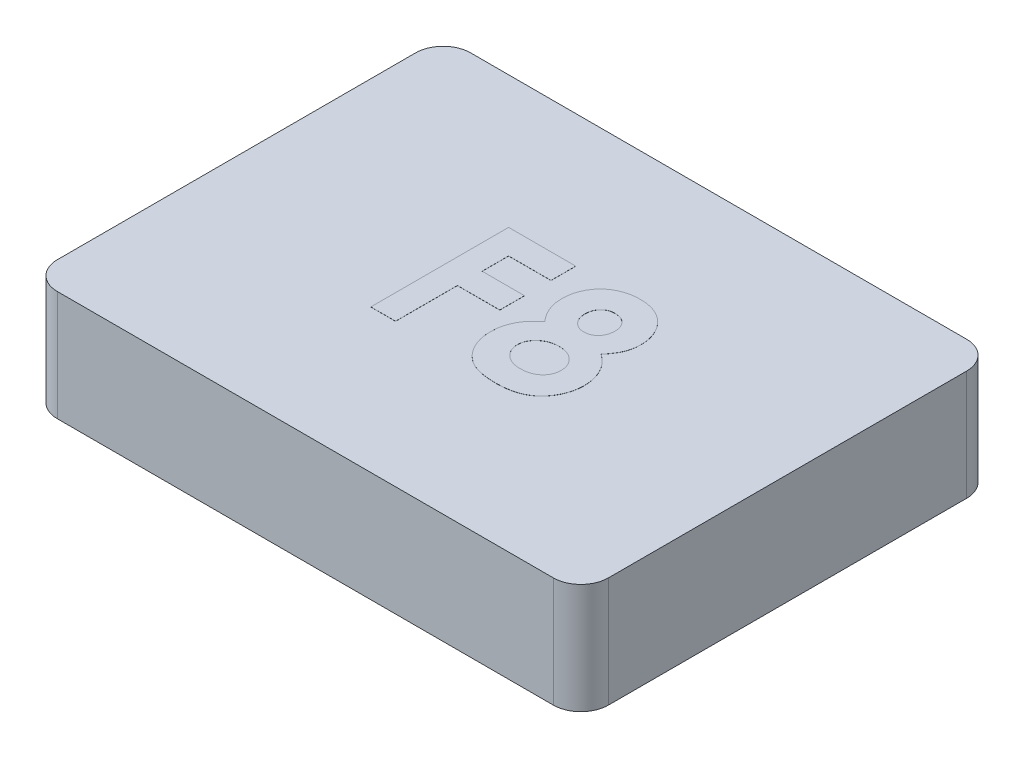
SolidWorks part; units mm, degrees
ref_plane "Front Plane" through (0, 0, 0) normal (0, 0, 1) x (1, 0, 0)
ref_plane "Top Plane" through (0, 0, 0) normal (0, 1, 0) x (1, 0, 0)
ref_plane "Right Plane" through (0, 0, 0) normal (1, 0, 0) x (0, 0, -1)
sketch "Sketch1" plane through (0, 0, 0) normal (0, 1, 0) x (1, 0, 0)
  line L0 (0, 0) -> (12.7, 0)
  line L1 (12.7, 0) -> (12.7, 9.525)
  line L2 (12.7, 9.525) -> (0, 9.525)
  line L3 (0, 9.525) -> (0, 0)
  dimension "D1" = 12.7
  dimension "D2" = 9.525
extrude "Boss-Extrude1" add sketch "Sketch1" along normal blind 2.54
fillet "Fillet1" radius 0.635 4 edges at (0, 1.27, -9.525) (12.7, 1.27, -9.525) (12.7, 1.27, 0) (0, 1.27, 0)
shell "Shell1" thickness 0.635 removed face at (6.35, 0, -4.7625)
sketch "Sketch2" plane through (0, 1.905, 0) normal (0, -1, 0) x (-1, 0, 0)
  line L0 (-0.635, 4.7625) -> (-12.065, 4.7625) construction
  line L1 (-0.635, 8.89) -> (-0.635, 0.635) construction
  line L2 (-12.065, 0.635) -> (-12.065, 8.89) construction
  line L3 (-6.35, 0.635) -> (-6.35, 8.89) construction
  line L4 (-0.635, 0.635) -> (-12.065, 0.635) construction
  line L5 (-12.065, 8.89) -> (-0.635, 8.89) construction
  circle A0 centre (-6.35, 4.7625) radius 2.54
  dimension "D1" = 5.08
extrude "Boss-Extrude2" add sketch "Sketch2" along normal up to surface (1.905 mm away) up to face at (6.35, 0, -4.7625)
sketch "Sketch3" plane through (0, 2.54, 0) normal (0, 1, 0) x (1, 0, 0)
  line L0 (0.635, 0) -> (12.065, 0) construction
  line L1 (0, 8.89) -> (0, 0.635) construction
  text T0 "<b>F8</b>"
  dimension "D1" = 3.302
  dimension "D2" = 4.191
extrude "Boss-Extrude3" add sketch "Sketch3" along normal blind 0.0025
